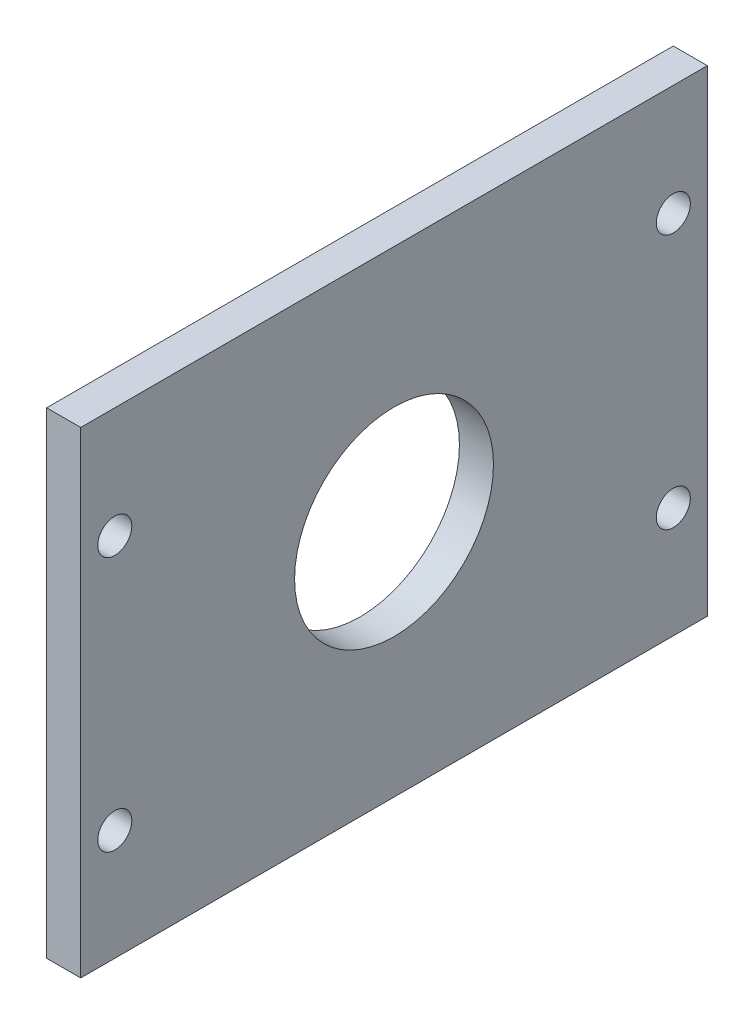
SolidWorks part; units mm, degrees
ref_plane "Front Plane" through (0, 0, 0) normal (0, 0, 1) x (1, 0, 0)
ref_plane "Top Plane" through (0, 0, 0) normal (0, 1, 0) x (1, 0, 0)
ref_plane "Right Plane" through (0, 0, 0) normal (1, 0, 0) x (0, 0, -1)
sketch "Sketch1" plane through (0, 0, 0) normal (1, 0, 0) x (0, 0, -1)
  line L0 (0, 0) -> (92, -70) construction
  line L1 (0, 0) -> (92, 0)
  line L2 (0, 0) -> (0, -70)
  line L3 (0, -70) -> (92, -70)
  line L4 (92, 0) -> (92, -70)
  line L5 (92, 0) -> (0, -70) construction
  line L6 (46, -35) -> (46, 0) construction
  line L7 (46, -17.5) -> (0, -17.5) construction
  circle A0 centre (46, -35) radius 14.6
  dimension "D3" = 29.2
  dimension "D1" = 70
  dimension "D2" = 92
extrude "Boss-Extrude1" add sketch "Sketch1" along normal blind 5
sketch "Sketch2" plane through (5, 0, 0) normal (1, 0, 0) x (0, 0, -1)
  line L0 (0, 0) -> (92, -70) construction
  line L1 (92, -70) -> (92, 0) construction
  line L2 (92, 0) -> (0, -70) construction
  circle A0 centre (5, -53.7276) radius 2.5
  circle A1 centre (5, -16.2724) radius 2.5
  circle A2 centre (87, -53.7276) radius 2.5
  circle A3 centre (87, -16.2724) radius 2.5
extrude "Cut-Extrude1" cut sketch "Sketch2" against normal through all both and the other way through all
